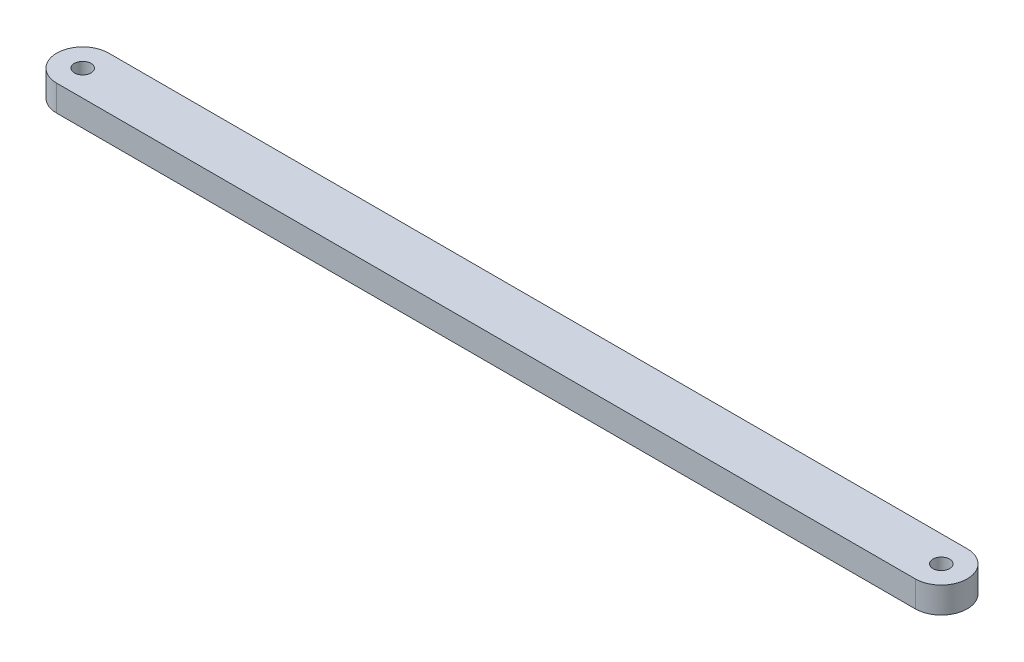
SolidWorks part; units mm, degrees
material "PET"
ref_plane "Front Plane" through (0, 0, 0) normal (0, 0, 1) x (1, 0, 0)
ref_plane "Top Plane" through (0, 0, 0) normal (0, 1, 0) x (1, 0, 0)
ref_plane "Right Plane" through (0, 0, 0) normal (1, 0, 0) x (0, 0, -1)
sketch "Sketch1" plane through (0, 0, 0) normal (0, 1, 0) x (1, 0, 0)
  line L0 (-165, 0) -> (165, 0) construction
  line L4 (-165, 10) -> (165, 10)
  line L5 (-165, -10) -> (165, -10)
  arc A3 (-165, 10) -> (-165, -10) centre (-165, 0) ccw
  arc A4 (165, -10) -> (165, 10) centre (165, 0) ccw
  circle A5 centre (-165, 0) radius 3.2
  circle A6 centre (165, 0) radius 3.2
  point P2 (0, 0)
  dimension "D3" = 6.4
  dimension "D4" = 6.4
  dimension "D1" = 20
  dimension "D2" = 330
extrude "Boss-Extrude1" add sketch "Sketch1" along normal blind 10
equation "\"D2@Sketch1\"=165+165"
